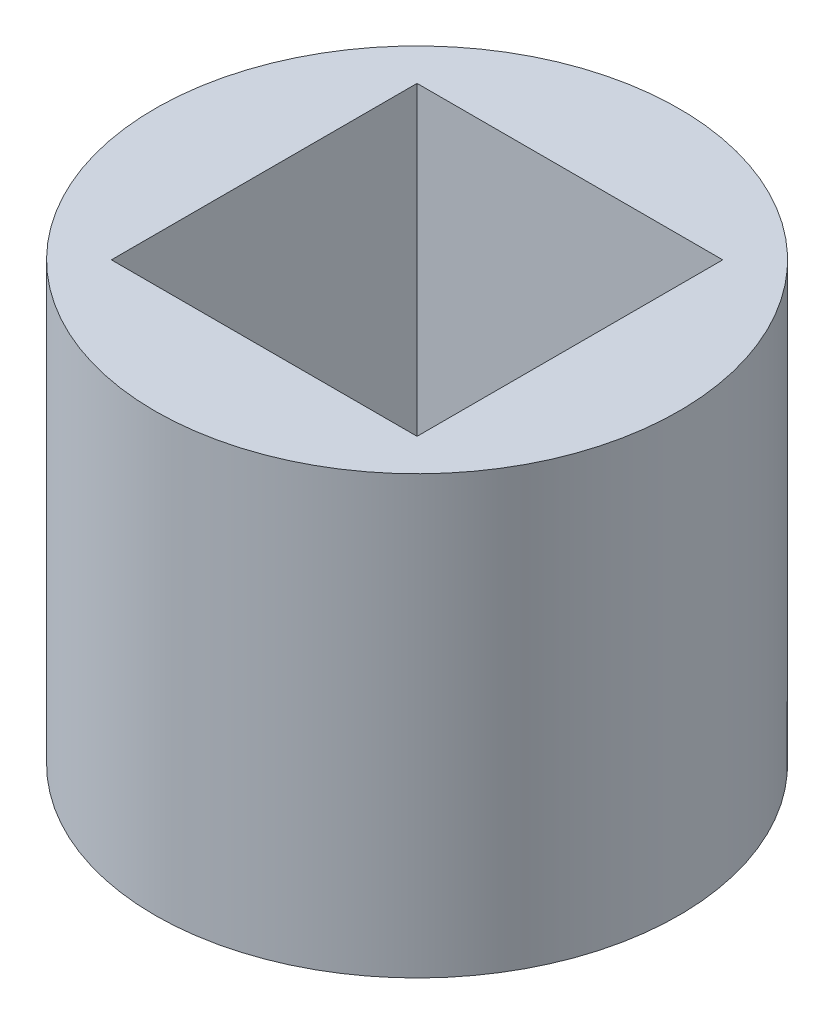
SolidWorks part; units mm, degrees
ref_plane "Front Plane" through (0, 0, 0) normal (0, 0, 1) x (1, 0, 0)
ref_plane "Top Plane" through (0, 0, 0) normal (0, 1, 0) x (1, 0, 0)
ref_plane "Right Plane" through (0, 0, 0) normal (1, 0, 0) x (0, 0, -1)
sketch "Sketch1" plane through (0, 0, 0) normal (0, 1, 0) x (1, 0, 0)
  line L0 (0, 0) -> (0, 8.89)
  line L1 (0, 8.89) -> (8.89, 8.89)
  line L2 (8.89, 8.89) -> (8.89, 0)
  line L3 (8.89, 0) -> (0, 0)
  circle A0 centre (4.445, 4.445) radius 7.62
  dimension "D3" = 15.24
  dimension "D1" = 8.89
  dimension "D2" = 8.89
extrude "Boss-Extrude1" add sketch "Sketch1" along normal blind 12.7
